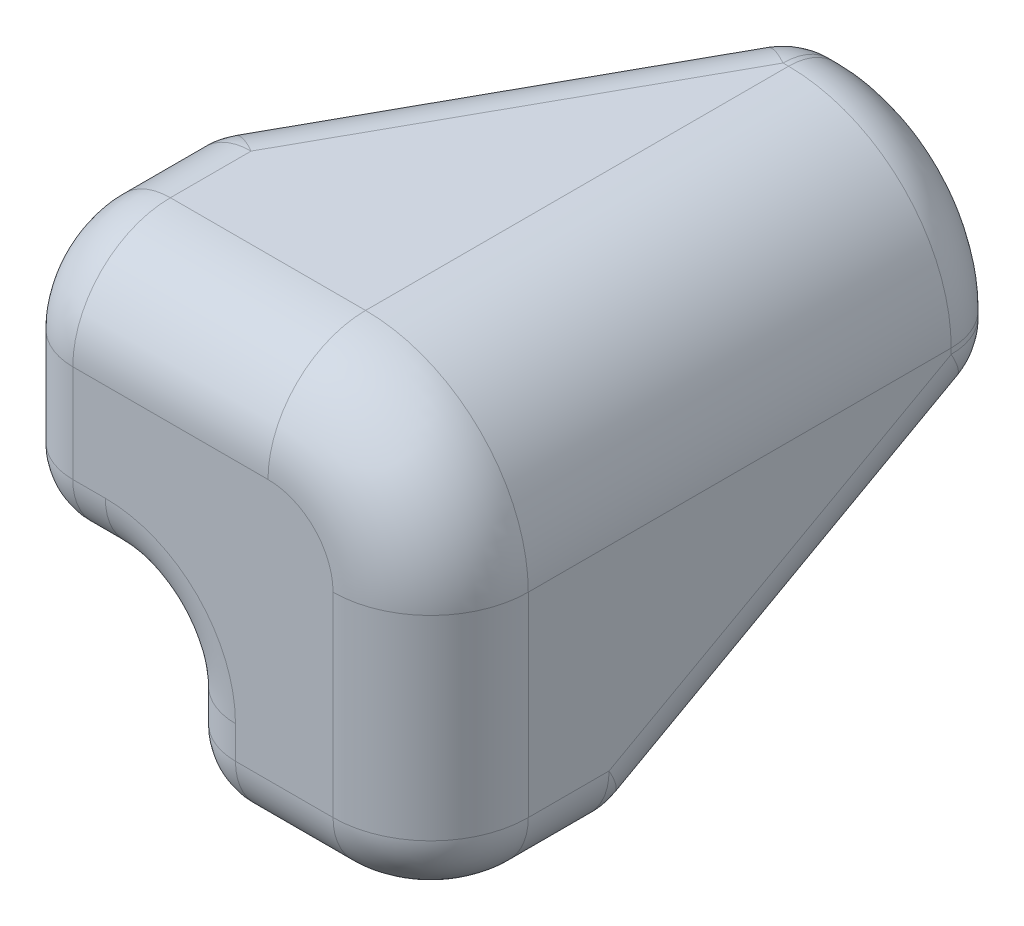
SolidWorks part; units mm, degrees
ref_plane "Front Plane" through (0, 0, 0) normal (0, 0, 1) x (1, 0, 0)
ref_plane "Top Plane" through (0, 0, 0) normal (0, 1, 0) x (1, 0, 0)
ref_plane "Right Plane" through (0, 0, 0) normal (1, 0, 0) x (0, 0, -1)
sketch "Sketch1" plane through (0, 0, 0) normal (0, 0, 1) x (1, 0, 0)
  line L0 (-10, 5) -> (-5, 5)
  line L1 (0, 0) -> (-5, 0)
  line L2 (0, 0) -> (0, 10)
  line L3 (0, 10) -> (-10, 10)
  line L4 (-10, 5) -> (-10, 10)
  line L5 (-5, 5) -> (-5, 0)
  dimension "D1" = 10
  dimension "D2" = 10
  dimension "D3" = 5
  dimension "D4" = 5
extrude "Boss-Extrude1" add sketch "Sketch1" along normal blind 3
sketch "Sketch2" plane through (0, 10, 0) normal (0, 1, 0) x (1, 0, 0)
  line L1 (-10, 0) -> (0, 0)
  line L2 (-10, 0) -> (-10, -3)
  line L3 (-10, -3) -> (0, -3)
  line L4 (0, 0) -> (0, -3)
extrude "Boss-Extrude2" add sketch "Sketch2" along normal blind 3
sketch "Sketch3" plane through (0, 0, 0) normal (1, 0, 0) x (0, 0, -1)
  line L1 (0, 13) -> (-3, 13)
  line L2 (0, 13) -> (0, 0)
  line L3 (0, 0) -> (-3, 0)
  line L4 (-3, 13) -> (-3, 0)
extrude "Boss-Extrude3" add sketch "Sketch3" along normal blind 3
sketch "Sketch4" plane through (0, 0, 0) normal (0, 0, -1) x (-1, 0, 0)
  line L0 (-3, 0) -> (-3, 13) construction
  line L1 (10, 13) -> (-3, 13)
  line L2 (10, 13) -> (10, 10)
  line L3 (10, 10) -> (0, 10)
  line L4 (-3, 13) -> (-3, 9.4592)
  line L6 (-3, 0) -> (0, 0)
  line L7 (-3, 0) -> (-3, 9.4592)
  line L9 (0, 0) -> (0, 10)
  dimension "D1" = 3
  dimension "D2" = 3
extrude "Boss-Extrude4" add sketch "Sketch4" along normal blind 15
fillet "Fillet1" radius 3 2 edges at (3, 6.5, 3) (-3.5, 13, 3)
fillet "Fillet2" radius 2 3 edges at (-5, 5, 1.5) (-10, 5, 1.5) (-5, 0, 1.5)
chamfer "Chamfer1" distance 12 angle 29 1 edges at (-10, 11.5, -15) first distance on face at (-10, 10.303, -4.4112)
fillet "Fillet3" radius 2 2 edges at (-3.3483, 11.5, -15) (-10, 11.5, -3)
chamfer "Chamfer2" distance 12 angle 29 1 edges at (1.5, 0, -15) first distance on face at (-0.1255, 0, -4.4112)
fillet "Fillet4" radius 2 2 edges at (1.5, 6.6517, -15) (1.5, 0, -3)
fillet "Fillet5" radius 5 2 edges at (2.1213, 12.1213, 2.1213) (3, 13, -7.5)
fillet "Fillet7" radius 2 20 edges at (3, 7.9149, -15) (3, 6.8147, -14.7233) (3, 3.1657, -8.711) (3, 0.0637, -2.9835) (3, 0, -1.2414) (2.1213, 0, 2.1213) (-1.5, 0, 3) (-4.4142, 0.5858, 3) (-5, 2.5, 3) (-5.5858, 4.4142, 3) (-7.5, 5, 3) (-9.4142, 5.5858, 3) (-10, 8.5, 3) (-10, 12.1213, 2.1213) (-2.0851, 13, -15) (1.5355, 11.5355, -15) (-3.1853, 13, -14.7233) (-10, 13, -1.2414) (-9.9363, 13, -2.9835) (-6.8343, 13, -8.711)
sketch "Sketch5" plane through (0, 0, 0) normal (0, 0, -1) x (-1, 0, 0)
  line L0 (10, 8) -> (10, 7)
  line L1 (7, 5) -> (8, 5)
  line L2 (5, 3) -> (5, 2)
  line L3 (3, 0) -> (2, 0)
  line L4 (3, 0) -> (0, 0) construction
  line L5 (2, 0) -> (2, 8)
  line L6 (2, 8) -> (10, 8)
  line L7 (0, 10) -> (10, 10) construction
  line L8 (0, 0) -> (0, 10) construction
  arc A0 (10, 7) -> (8, 5) centre (8, 7) cw
  arc A1 (7, 5) -> (5, 3) centre (7, 3) ccw
  arc A2 (5, 2) -> (3, 0) centre (3, 2) cw
  dimension "D1" = 2
  dimension "D2" = 2
extrude "Boss-Extrude5" add sketch "Sketch5" along normal blind 2
